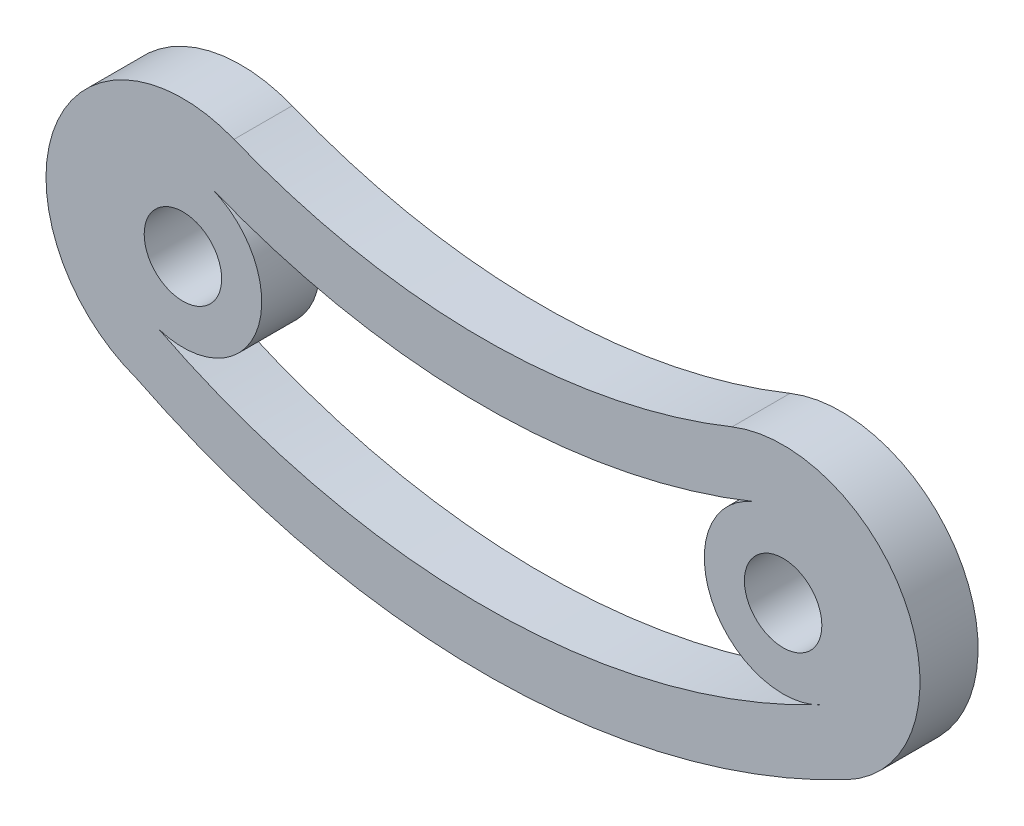
SolidWorks part; units mm, degrees
material "Plain Carbon Steel"
ref_plane "Front Plane" through (0, 0, 0) normal (0, 0, 1) x (1, 0, 0)
ref_plane "Top Plane" through (0, 0, 0) normal (0, 1, 0) x (1, 0, 0)
ref_plane "Right Plane" through (0, 0, 0) normal (1, 0, 0) x (0, 0, -1)
sketch "Sketch1" plane through (0, 0, 0) normal (0, 0, 1) x (1, 0, 0)
  line L0 (0, 0) -> (31, 0)
  line L1 (0, -5) -> (31, -5)
  line L2 (0, 5) -> (31, 5)
  circle A0 centre (31, 0) radius 1.5
  circle A1 centre (0, 0) radius 1.5
  arc A2 (0, -5) -> (0, 5) centre (0, 0) cw
  arc A3 (31, -5) -> (31, 5) centre (31, 0) ccw
  dimension "D1" = 3
extrude "Extrude1" add sketch "Sketch1" along normal blind 3 contours L1 A3 L2 A2 A1 A0 region at (-4.578, 0, 0)
sketch "Sketch2" plane through (0, 0, 3) normal (0, 0, 1) x (1, 0, 0)
  line L1 (15.5, 5) -> (15.5, -10)
  line L2 (0, 5) -> (31, 5) construction
  arc A0 (36, 0) -> (-5, 0) centre (15.5, 16.0125) cw
  arc A1 (36, 0) -> (31, 5) centre (33.5, 2.5) ccw
  arc A2 (31, -5) -> (31, 5) centre (31, 0) ccw construction
  arc A3 (0, 5) -> (0, -5) centre (0, 0) ccw construction
  arc A4 (31, 5) -> (0, 5) centre (15.5, 21.0125) cw
  arc A5 (-5, 0) -> (0, 5) centre (-2.5, 2.5) cw
  line M3 (0, -5) -> (31, -5)
  arc M4 (31, -5) -> (31, 5) centre (31, 0) ccw
  line M5 (31, 5) -> (0, 5)
  arc M6 (0, 5) -> (0, -5) centre (0, 0) ccw
  dimension "D2" = 5
  dimension "D1" = 15
extrude "Boss-Extrude2" add sketch "Sketch2" against normal blind 3 contours A1 M4 | A0 L1 M3 | A0 L1 M3 | A5 M6 region at (21.3318, -7.0174, 3) region at (9.6682, -7.0174, 3) region at (34.927, 3.927, 3) region at (-3.927, 3.927, 3)
extrude "Cut-Extrude4" cut sketch "Sketch2<6>" against normal blind 5 contours A0 M4 M3 | A0 M3 M6 | A4 L1 M5 | A4 L1 M5 region at (21.4396, 2.4578, 3) region at (9.5604, 2.4578, 3) region at (33.916, -3.0126, 3) region at (-2.916, -3.0126, 3)
sketch "Sketch2<6>" plane through (0, 0, 3) normal (0, 0, 1) x (1, 0, 0) same geometry as "Sketch2"
sketch "Sketch5" plane through (0, 0, 0) normal (0, 0, -1) x (-1, 0, 0)
  circle A0 centre (0, 0) radius 7.0711
  circle A1 centre (-31, 0) radius 7.0711
  arc M7 (0, 5) -> (-31, 5) centre (-15.5, 21.0125) cw
  arc M8 (-31, 5) -> (-36, 0) centre (-33.5, 2.5) ccw
  arc M9 (-36, 0) -> (5, 0) centre (-15.5, 16.0125) ccw
  arc M10 (5, 0) -> (0, 5) centre (2.5, 2.5) ccw
extrude "Boss-Extrude3" add sketch "Sketch5" against normal blind 3 contours A1 M7 M8 | A1 M8 M9 | A0 M10 M7 | A0 M9 M10 region at (-3.5179, -3.3541, 0) region at (2.7948, 4.3745, 0) region at (34.5179, -3.3541, 0) region at (28.2052, 4.3745, 0)
sketch "Sketch6" plane through (0, 0, 0) normal (0, 0, -1) x (-1, 0, 0)
  arc A0 (-2.6395, 6.5599) -> (-28.3605, 6.5599) centre (-15.5, 38.5218) cw
  arc A1 (-2.5997, -6.5758) -> (-7.0605, 0.3867) centre (0, 0) ccw construction
  arc A2 (-23.9395, 0.3867) -> (-28.4003, -6.5758) centre (-31, 0) ccw construction
  arc A3 (2.3961, -6.6527) -> (-34.2887, -6.2598) centre (-15.5624, 29.3845) cw
  arc M1 (-23.9395, 0.3867) -> (-28.4003, -6.5758) centre (-31, 0) ccw
  arc M2 (-28.4003, -6.5758) -> (-2.5997, -6.5758) centre (-15.5, 16.0125) ccw
  arc M3 (-2.5997, -6.5758) -> (-7.0605, 0.3867) centre (0, 0) ccw
  arc M4 (-7.0605, 0.3867) -> (-23.9395, 0.3867) centre (-15.5, 21.0125) cw
extrude "Boss-Extrude4" add sketch "Sketch6" against normal blind 3 contours A0 M3 M1 M4 | A3 M3 M2 M1 region at (15.5, 2.0626, 0) region at (15.9897, -10.5074, 0)
sketch "Sketch7" plane through (0, 0, 0) normal (0, 0, -1) x (-1, 0, 0)
  circle A0 centre (0, 0) radius 2
  circle A1 centre (-31, 0) radius 2
  circle A4 centre (-31, 0) radius 4.0711
  circle A5 centre (0, 0) radius 4.0711
  arc A8 (-32.8934, -3.604) -> (1.2332, -3.8798) centre (-15.5624, 29.3845) ccw
  arc A9 (-32.8934, -3.604) -> (1.2332, -3.8798) centre (-15.5624, 29.3845) ccw
  arc A10 (1.2332, -3.8798) -> (-1.5197, 3.7768) centre (0, 0) ccw
  arc A11 (1.2332, -3.8798) -> (-1.5197, 3.7768) centre (0, 0) ccw
  arc A12 (-29.4803, 3.7768) -> (-1.5197, 3.7768) centre (-15.5, 38.5218) ccw
  arc A13 (-29.4803, 3.7768) -> (-1.5197, 3.7768) centre (-15.5, 38.5218) ccw
  arc A14 (-29.4803, 3.7768) -> (-32.8934, -3.604) centre (-31, 0) ccw
  arc A15 (-29.4803, 3.7768) -> (-32.8934, -3.604) centre (-31, 0) ccw
  dimension "D2" = 4
  dimension "D3" = 4
  dimension "D1" = 3
extrude "Cut-Extrude6" cut sketch "Sketch7" against normal blind 5 contours A13 A4 A9 A5 | A1 | A0 region at (15.5258, -2.8514, 0)
move or copy body "Body-Move/Copy1" [suppressed] bodies to move or copy 112
move or copy body "Body-Move/Copy2" [suppressed] bodies to move or copy 112
move or copy body "Body-Move/Copy3" [suppressed] bodies to move or copy 112
